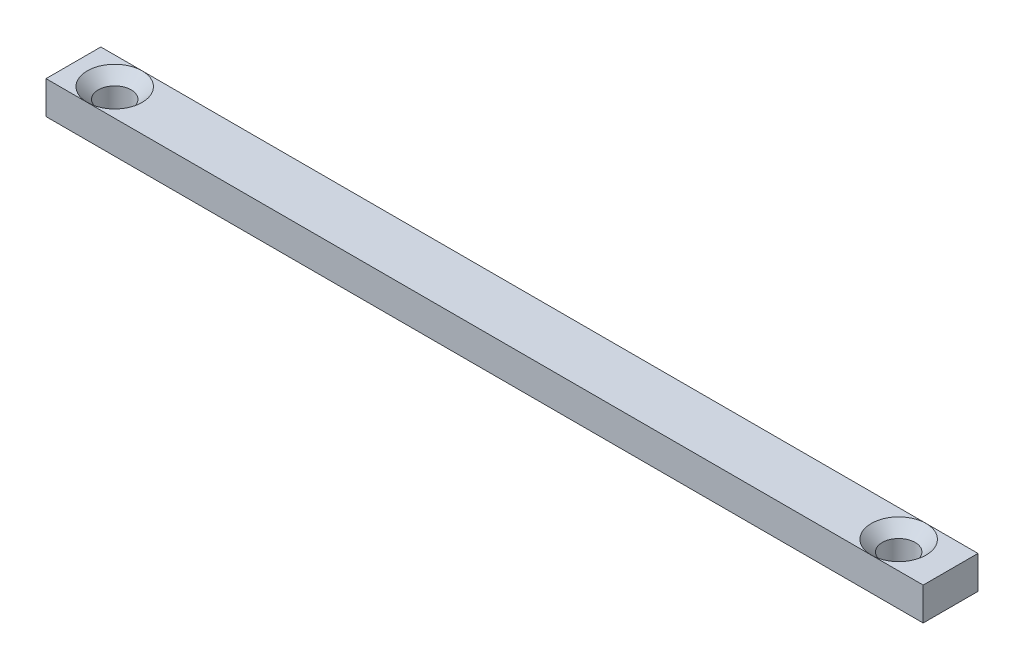
SolidWorks part; units mm, degrees
ref_plane "Front Plane" through (0, 0, 0) normal (0, 0, 1) x (1, 0, 0)
ref_plane "Top Plane" through (0, 0, 0) normal (0, 1, 0) x (1, 0, 0)
ref_plane "Right Plane" through (0, 0, 0) normal (1, 0, 0) x (0, 0, -1)
sketch "Sketch1" plane through (0, 0, 0) normal (0, 1, 0) x (1, 0, 0)
  line L0 (-31.9743, 4.9193) -> (48.0257, 4.9193) construction
  line L1 (-31.9743, 7.4193) -> (48.0257, 7.4193)
  line L2 (-31.9743, 7.4193) -> (-31.9743, 2.4193)
  line L3 (-31.9743, 2.4193) -> (48.0257, 2.4193)
  line L4 (48.0257, 7.4193) -> (48.0257, 2.4193)
  circle A0 centre (-28.2082, 4.9193) radius 1.5
  circle A1 centre (43.2918, 4.9193) radius 1.5
  circle A2 centre (43.2918, 4.9193) radius 2.1 construction
  point P10 (0, 0)
  dimension "D3" = 3
  dimension "D4" = 3
  dimension "D1" = 80
  dimension "D2" = 5
extrude "Boss-Extrude1" add sketch "Sketch1" along normal blind 3
chamfer "Chamfer1" distance 1 angle 45 2 edges at (43.2918, 3, -3.4193) (-28.2082, 3, -3.4193)
